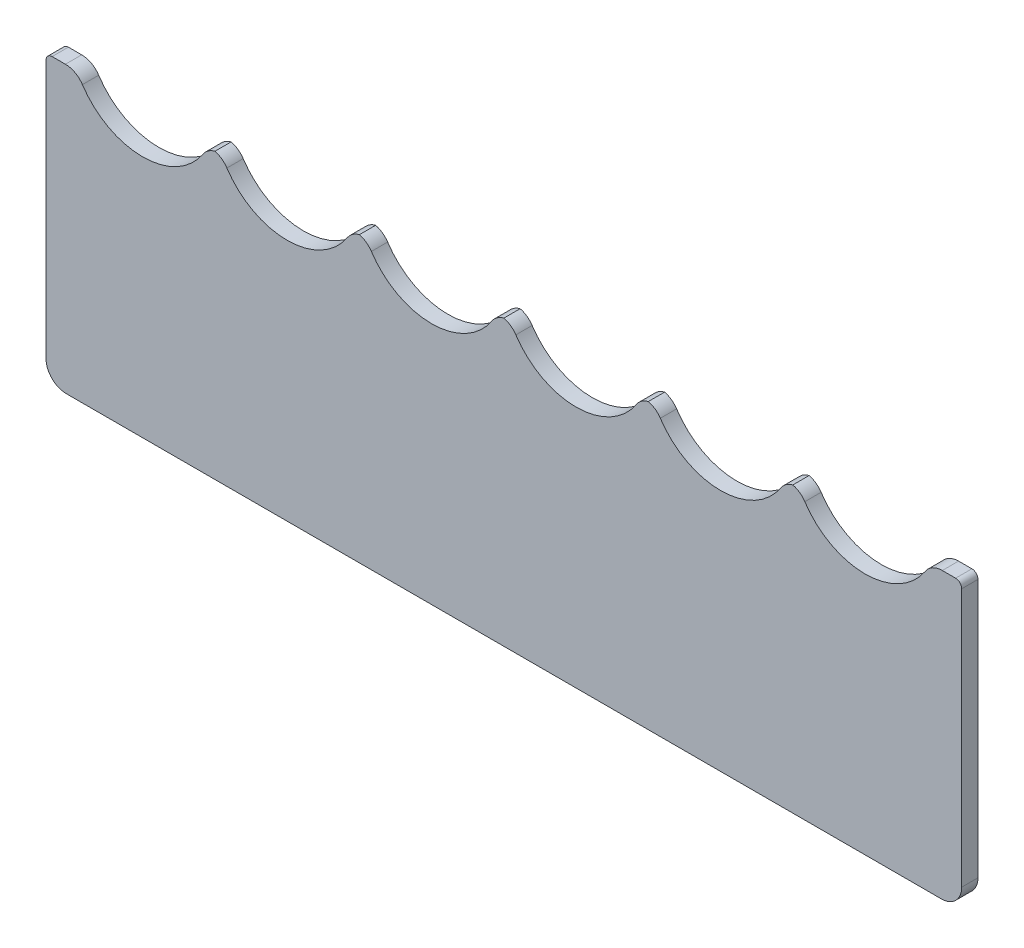
SolidWorks part; units mm, degrees
ref_plane "Plan de face" through (0, 0, 0) normal (0, 0, 1) x (1, 0, 0)
ref_plane "Plan de dessus" through (0, 0, 0) normal (0, 1, 0) x (1, 0, 0)
ref_plane "Plan de droite" through (0, 0, 0) normal (1, 0, 0) x (0, 0, -1)
sketch "Esquisse1" plane through (0, 0, 0) normal (0, 0, 1) x (1, 0, 0)
  line L0 (225, 0) -> (225, 140) construction
  line L1 (0, 0) -> (450, 0)
  line L2 (0, 0) -> (0, 140)
  line L3 (0, 140) -> (450, 140)
  line L4 (450, 0) -> (450, 140)
  dimension "D1" = 450
  dimension "D2" = 140
extrude "Boss.-Extru.1" add sketch "Esquisse1" along normal blind 8
sketch "Esquisse2" plane through (0, 0, 8) normal (0, 0, 1) x (1, 0, 0)
  line L0 (225, 0) -> (225, 140) construction
  line L1 (0, 0) -> (450, 0) construction
  line L2 (450, 140) -> (0, 140) construction
  line L3 (189.5, 155) -> (189.5, 75.8534) construction
  line L4 (189.5, 75.8534) -> (225, 75.8534) construction
  line L5 (47.5, 155) -> (118.5, 155) construction
  line L6 (118.5, 155) -> (189.5, 155) construction
  line L7 (331.5, 155) -> (260.5, 155) construction
  line L8 (402.5, 155) -> (331.5, 155) construction
  circle A0 centre (189.5, 155) radius 35.45
  circle A1 centre (118.5, 155) radius 35.45
  circle A2 centre (47.5, 155) radius 35.45
  circle A3 centre (402.5, 155) radius 35.45
  circle A4 centre (331.5, 155) radius 35.45
  circle A5 centre (260.5, 155) radius 35.45
  dimension "D1" = 70.9
  dimension "D2" = 71
  dimension "D3" = 71
  dimension "D5" = 15
  dimension "D4" = 35.5
extrude "Enlèv. mat.-Extru.1" cut sketch "Esquisse2" against normal through all both and the other way through all
fillet "Congé1" radius 10 14 edges at (15.3799, 140, 4) (434.6201, 140, 4) (370.3799, 140, 4) (363.6201, 140, 4) (299.3799, 140, 4) (292.6201, 140, 4) (228.3799, 140, 4) (221.6201, 140, 4) (157.3799, 140, 4) (150.6201, 140, 4) (86.3799, 140, 4) (79.6201, 140, 4) (450, 0, 4) (0, 0, 4)
fillet "Congé2" radius 3 2 edges at (450, 140, 4) (0, 140, 4)
